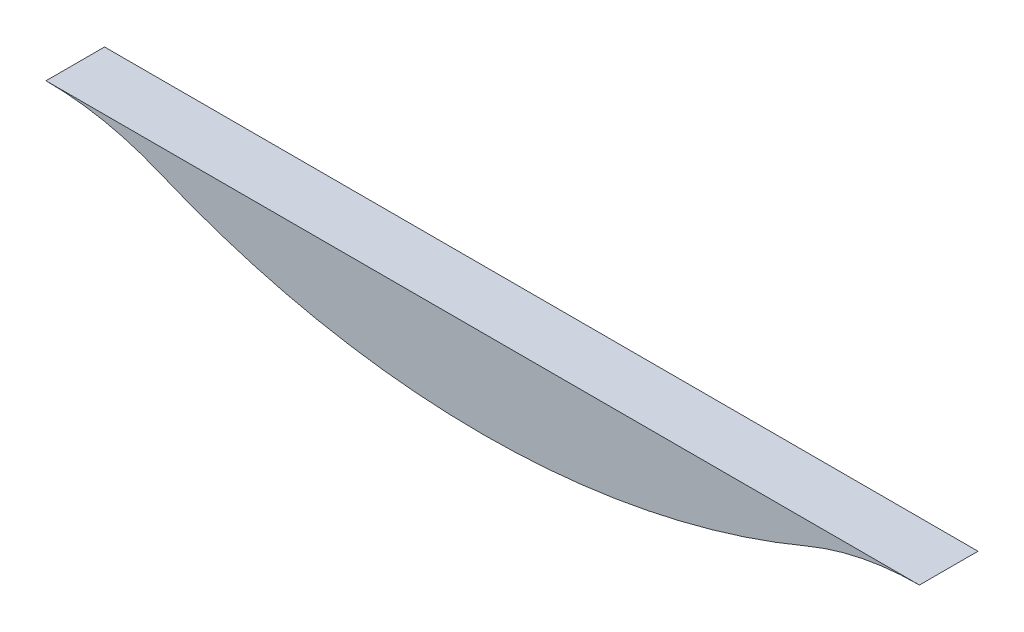
SolidWorks part; units mm, degrees
ref_plane "Plane1" through (0, 0, 0) normal (0, 0, 1) x (1, 0, 0)
ref_plane "Plane2" through (0, 0, 0) normal (0, 1, 0) x (1, 0, 0)
ref_plane "Plane3" through (0, 0, 0) normal (1, 0, 0) x (0, 0, -1)
sketch "Sketch1" plane through (0, 0, 0) normal (0, 0, 1) x (1, 0, 0)
  line L0 (-43.4634, 0) -> (43.4634, 0)
  line L1 (-43.4634, 0) -> (-43.4634, 6.7208)
  line L2 (43.4634, 6.7208) -> (-43.4634, 6.7208)
  line L3 (43.4634, 6.7208) -> (43.4634, 0)
  line L4 (50, 0) -> (-50, 0) construction
  line L5 (0, 0) -> (0, 6.7208) construction
extrude "Base-Extrude" add sketch "Sketch1" along normal mid plane 40
sketch "Sketch2" plane through (0, 0, 0) normal (0, 0, 1) x (1, 0, 0)
  line L0 (-43.4634, 0) -> (43.4634, 0) construction
  line L1 (0, -50) -> (0, 50) construction
  line L2 (-12.75, 0) -> (12.75, 0)
  arc A0 (-12.75, 0) -> (12.75, 0) centre (0, 25.5937) ccw
  dimension "D1" = 3
  dimension "D2" = 25.5
extrude "Boss-Extrude1" add sketch "Sketch2" along normal mid plane 2
fillet "Fillet1" radius 10 2 edges at (12.75, 0, 0) (-12.75, 0, 0)
sketch "Sketch3" plane through (43.4634, 0, 0) normal (1, 0, 0) x (0, 0, -1)
  line L4 (-20, 6.7208) -> (20, 6.7208)
  line L5 (-20, 6.7208) -> (-20, 0)
  line L6 (-20, 0) -> (20, 0)
  line L7 (20, 6.7208) -> (20, 0)
  line L8 (-20, 6.7208) -> (20, 6.7208)
  line L9 (-20, 6.7208) -> (-20, 0)
  line L10 (-20, 0) -> (20, 0)
  line L11 (20, 6.7208) -> (20, 0)
  dimension "D1" = 0
extrude "Cut-Extrude1" cut sketch "Sketch3" against normal through all
sketch "Orientation sketch" plane through (0, 0, 0) normal (0, 1, 0) x (-1, 0, 0)
  line L4 (14.9185, -1) -> (-14.9185, -1)
  line L5 (14.9185, -1) -> (14.9185, 1)
  line L6 (14.9185, 1) -> (-14.9185, 1)
  line L7 (-14.9185, 1) -> (-14.9185, -1)
  line L8 (14.9185, -1) -> (-14.9185, -1)
  line L9 (14.9185, -1) -> (14.9185, 1)
  line L10 (14.9185, 1) -> (-14.9185, 1)
  line L11 (-14.9185, 1) -> (-14.9185, -1)
  dimension "D1" = 0
